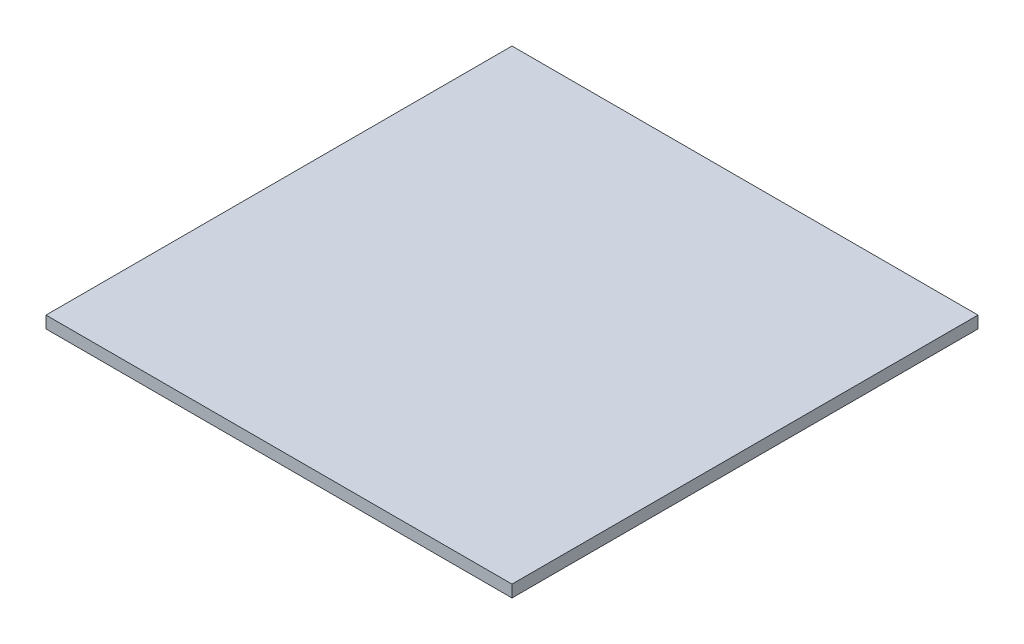
SolidWorks part; units mm, degrees
ref_plane "前视基准面" through (0, 0, 0) normal (0, 0, 1) x (1, 0, 0)
ref_plane "上视基准面" through (0, 0, 0) normal (0, 1, 0) x (1, 0, 0)
ref_plane "右视基准面" through (0, 0, 0) normal (1, 0, 0) x (0, 0, -1)
other "Configuration Table"
sketch "草图1" plane through (0, 0, 0) normal (0, 1, 0) x (1, 0, 0)
  line L1 (0, 0) -> (-310, 0)
  line L2 (0, 0) -> (0, 310)
  line L3 (0, 310) -> (-310, 310)
  line L4 (-310, 0) -> (-310, 310)
  dimension "D1" = 310
  dimension "D2" = 310
extrude "凸台-拉伸1" add sketch "草图1" along normal blind 8
